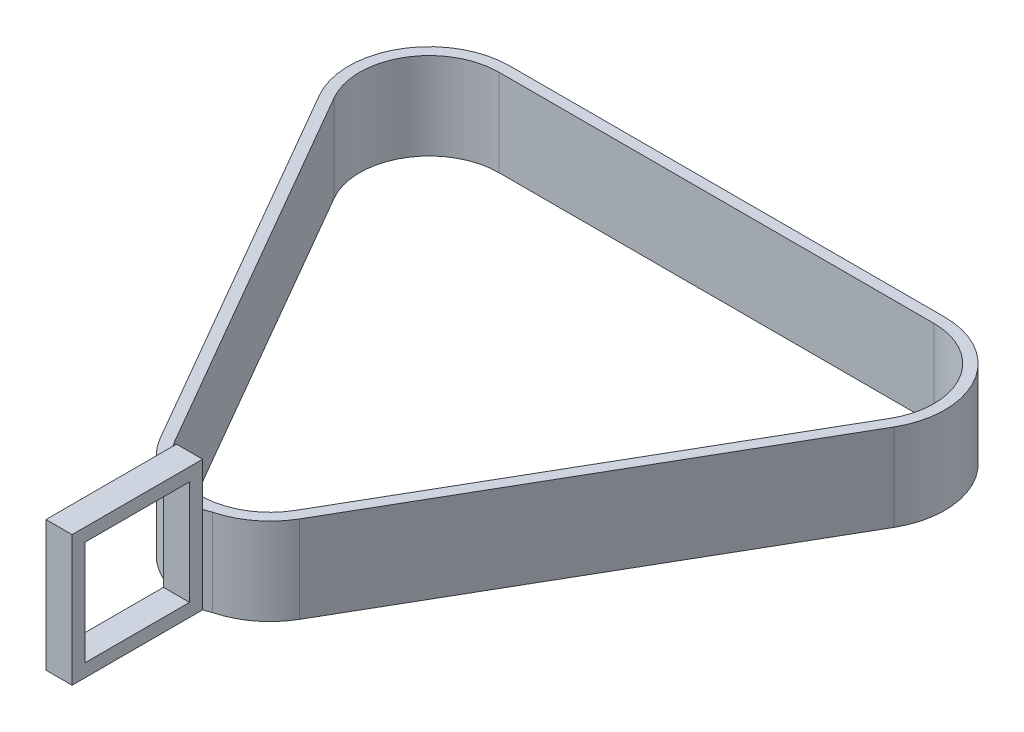
SolidWorks part; units mm, degrees
ref_plane "Front Plane" through (0, 0, 0) normal (0, 0, 1) x (1, 0, 0)
ref_plane "Top Plane" through (0, 0, 0) normal (0, 1, 0) x (1, 0, 0)
ref_plane "Right Plane" through (0, 0, 0) normal (1, 0, 0) x (0, 0, -1)
sketch "Sketch1" plane through (0, 0, 0) normal (0, 1, 0) x (1, 0, 0)
  line L0 (0, 0) -> (100, 0)
  line L1 (100, 0) -> (50, -86.6025)
  line L2 (50, -86.6025) -> (0, 0)
  line L3 (-13.8564, -8) -> (36.1436, -94.6025)
  line L4 (113.8564, -8) -> (63.8564, -94.6025)
  line L5 (100, 16) -> (0, 16)
  line L6 (100, 18.5) -> (0, 18.5)
  line L7 (-16.0215, -9.25) -> (33.9785, -95.8525)
  line L8 (66.0215, -95.8525) -> (116.0215, -9.25)
  circle A0 centre (100, 0) radius 16
  circle A1 centre (50, -86.6025) radius 16
  circle A2 centre (0, 0) radius 16
  circle A5 centre (100, 0) radius 18.5
  circle A6 centre (0, 0) radius 18.5
  circle A7 centre (50, -86.6025) radius 18.5
  dimension "D2" = 32
  dimension "D3" = 37
  dimension "D1" = 100
extrude "Boss-Extrude1" add sketch "Sketch1" along normal blind 20 contours A7 L3 A6 L7 | A7 L4 A1 L3 | A7 L8 A5 L4 | L4 A5 L5 A0 | A6 L5 A5 L6 | L5 A6 L3 A2 region at (-14.2403, 0, -8.2217) region at (50, 0, -17.285) region at (10.0307, 0, 51.9438) region at (95.3064, 0, -17.436) region at (33.4634, 0, 90.788) region at (89.9693, 0, 51.9438)
ref_plane "Plane1" through (50, 0, 0) normal (-1, 0, 0) x (0, 0, 1)
sketch "Sketch2" plane through (50, 0, 0) normal (-1, 0, 0) x (0, 0, 1)
  line L1 (105.1025, 0) -> (135.1025, 0)
  line L2 (105.1025, 0) -> (105.1025, 30)
  line L3 (105.1025, 30) -> (135.1025, 30)
  line L4 (135.1025, 0) -> (135.1025, 30)
  line L5 (108.1025, 3) -> (132.1025, 3)
  line L6 (108.1025, 3) -> (108.1025, 27)
  line L7 (108.1025, 27) -> (132.1025, 27)
  line L8 (132.1025, 3) -> (132.1025, 27)
  dimension "D1" = 30
  dimension "D2" = 30
  dimension "D3" = 24
  dimension "D4" = 24
  dimension "D5" = 3
  dimension "D6" = 3
extrude "Boss-Extrude2" add sketch "Sketch2" along normal blind 3 and the other way blind 3 separate body
sketch "Sketch3" plane through (0, 30, 0) normal (0, 1, 0) x (1, 0, 0)
  line L0 (47, -105.1025) -> (42.2916, -103.4201)
  line L1 (42.2916, -103.4201) -> (57.7084, -103.4201)
  line L2 (57.7084, -103.4201) -> (53, -105.1025)
  line L7 (53, -105.1025) -> (47, -105.1025)
  line L8 (47, -105.1025) -> (47, -135.1025)
  line L9 (47, -135.1025) -> (53, -135.1025)
  line L10 (53, -135.1025) -> (53, -105.1025)
  line L12 (47, -105.1025) -> (47, -135.1025)
  line L13 (47, -135.1025) -> (53, -135.1025)
  line L14 (53, -135.1025) -> (53, -105.1025)
  arc A0 (33.9785, -95.8525) -> (66.0215, -95.8525) centre (50, -86.6025) ccw construction
  line M2 (53, -105.1025) -> (47, -105.1025)
  dimension "D1" = 5
  dimension "D2" = 0
extrude "Boss-Extrude3" add sketch "Sketch3" against normal blind 30 contours L2 L1 L0 M2 region at (50, 30, 104.138)
sketch "Sketch4" plane through (50, 0, 0) normal (-1, 0, 0) x (0, 0, 1)
  line L1 (103.4201, 20) -> (105.1025, 20)
  line L2 (103.4201, 20) -> (103.4201, 30)
  line L3 (103.4201, 30) -> (105.1025, 30)
  line L4 (105.1025, 20) -> (105.1025, 30)
extrude "Cut-Extrude1" cut sketch "Sketch4" against normal blind 30 and the other way blind 30
